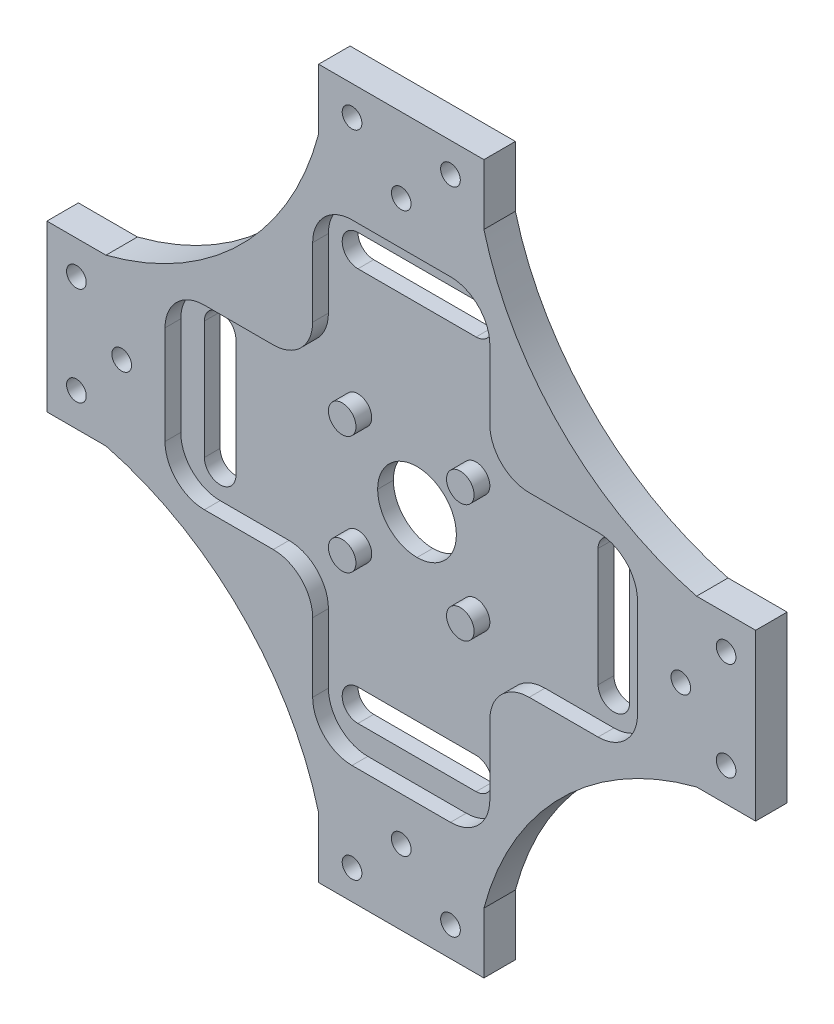
SolidWorks part; units mm, degrees
ref_plane "Front Plane" through (0, 0, 0) normal (0, 0, 1) x (1, 0, 0)
ref_plane "Top Plane" through (0, 0, 0) normal (0, 1, 0) x (1, 0, 0)
ref_plane "Right Plane" through (0, 0, 0) normal (1, 0, 0) x (0, 0, -1)
sketch "Sketch1" plane through (0, 0, 0) normal (0, 0, 1) x (1, 0, 0)
  line L13 (-90, -90) -> (90, -90)
  line L14 (-90, -90) -> (-90, 90)
  line L15 (-90, 90) -> (90, 90)
  line L16 (90, -90) -> (90, 90)
  line L17 (-90, -90) -> (90, 90) construction
  line L18 (-90, 90) -> (90, -90) construction
  line L19 (-75, -75) -> (75, -75)
  line L20 (-75, -75) -> (-75, 75)
  line L21 (-75, 75) -> (75, 75)
  line L22 (75, -75) -> (75, 75)
  line L23 (-75, -75) -> (75, 75) construction
  line L24 (-75, 75) -> (75, -75) construction
  line L39 (-75, -24.9122) -> (-75, 26.5574)
  line L40 (75, 22.5) -> (75, -22.5)
  line L41 (75, -22.5) -> (90, -20.9897)
  line L42 (90, -20.9897) -> (90, 20.9897)
  line L43 (90, 20.9897) -> (75, 22.5)
  line L44 (20.9897, -90) -> (22.5, -75)
  line L45 (22.5, -75) -> (-22.5, -75)
  line L46 (-22.5, -75) -> (-20.9897, -90)
  line L47 (-20.9897, -90) -> (20.9897, -90)
  line L48 (-90, -20.9897) -> (-75, -22.5)
  line L49 (-75, -22.5) -> (-75, 22.5)
  line L50 (-75, 22.5) -> (-90, 20.9897)
  line L51 (-90, 20.9897) -> (-90, -20.9897)
  line L52 (-20.9897, 90) -> (-22.5, 75)
  line L53 (-22.5, 75) -> (22.5, 75)
  line L54 (22.5, 75) -> (20.9897, 90)
  line L55 (20.9897, 90) -> (-20.9897, 90)
  line L64 (-72, -72) -> (-72, 72)
  line L65 (-72, 72) -> (72, 72)
  line L70 (72, -72) -> (72, 72)
  line L71 (-72, -72) -> (72, -72)
  line L72 (-10.5, -75) -> (10.5, -75)
  line L77 (75, -10.5) -> (64, -10.5)
  line L78 (75, -10.5) -> (75, 10.5)
  line L79 (75, 10.5) -> (64, 10.5)
  line L80 (64, -10.5) -> (64, 10.5)
  line L81 (-10.5, -75) -> (-10.5, -64)
  line L82 (-10.5, -64) -> (10.5, -64)
  line L83 (10.5, -75) -> (10.5, -64)
  line L84 (-75, 10.5) -> (-75, -10.5)
  line L85 (-75, 10.5) -> (-64, 10.5)
  line L86 (-64, 10.5) -> (-64, -10.5)
  line L87 (-75, -10.5) -> (-64, -10.5)
  line L88 (10.5, 75) -> (-10.5, 75)
  line L89 (10.5, 75) -> (10.5, 64)
  line L90 (10.5, 64) -> (-10.5, 64)
  line L91 (-10.5, 75) -> (-10.5, 64)
  line L92 (-75, 45) -> (-72, 45)
  line L93 (-45, 75) -> (-45, 72)
  circle A0 centre (82.5, 12.5) radius 2.5
  circle A1 centre (71, 0) radius 2.5
  circle A2 centre (82.5, -12.5) radius 2.5
  circle A3 centre (12.5, -82.5) radius 2.5
  circle A4 centre (0, -71) radius 2.5
  circle A5 centre (-12.5, -82.5) radius 2.5
  circle A6 centre (-82.5, -12.5) radius 2.5
  circle A7 centre (-71, 0) radius 2.5
  circle A8 centre (-82.5, 12.5) radius 2.5
  circle A9 centre (-12.5, 82.5) radius 2.5
  circle A10 centre (0, 71) radius 2.5
  circle A11 centre (12.5, 82.5) radius 2.5
  point P0 (0, 0)
  point P11 (0, 0)
  point P74 (64, 0)
  point P85 (0, 0)
  dimension "D3" = 4
  dimension "D1" = 180
  dimension "D2" = 180
  dimension "D4" = 150
  dimension "D5" = 4
  dimension "D6" = 3
  dimension "D8" = 11
  dimension "D7" = 21
  dimension "D10" = 45
  dimension "D11" = 45
  dimension "D9" = 4
extrude "Boss-Extrude1" add sketch "Sketch1" along normal mid plane 8 contours L19 L22 L21 L20 A10 A7 A4 A1 | L42 L15 L40 L21 A11 A9 | L47 L16 L45 L22 A2 A0 | L14 L20 A8 A6 | L51 L13 L49 L19 A5 A3 | A1 L79 L80 L77 | A1 L77 L40 L79 | L91 L21 L20 L39 L85 L64 L65 | A10 L65 L89 L53 L91 | A10 L65 L91 L90 L89 | A4 L71 L83 L82 L81 | A4 L71 L81 L45 L83 | L83 L19 L22 L77 L70 L71 | A7 L64 L87 L86 L85 | A7 L64 L85 L49 L87 | L91 L65 L64 L85 L86 L87 L71 L81 L82 L83 L70 L77 L80 L79 L89 L90 | L21 L93 L65 L91 | L21 L89 L65 L70 L79 L22 | L93 L21 L20 L92 L64 L65 region at (0, -82.4076, 0) region at (-82.4076, 0, 0) region at (-48.75, -74.0878, 0) region at (16.5, -74.0878, 0) region at (0, -73.5752, 0) region at (-73.5, 27.75, 0) region at (-73.5752, 0, 0) region at (82.4076, 0, 0) region at (0, -67.765, 0) region at (0, 0, 0) region at (0, 82.4076, 0) region at (-67.765, 0, 0) region at (-27.75, 73.5, 0) region at (-74.5757, 60, 0) region at (74.0878, 16.5, 0) region at (73.5752, 0, 0) region at (0, 73.5752, 0) region at (67.765, 0, 0) region at (0, 67.765, 0)
sketch "Sketch6" plane through (0, 0, 0) normal (0, 0, 1) x (1, 0, 0)
  line L7 (-15, 50) -> (15, 50) construction
  line L9 (-15, 54) -> (15, 54)
  line L16 (0, -55) -> (0, 55) construction
  line L18 (55, 0) -> (-55, 0) construction
  line L24 (-15, 46) -> (15, 46)
  line L25 (-20.9897, -90) -> (20.9897, -90)
  line L26 (-20.9897, -90) -> (-20.9897, 90)
  line L27 (-20.9897, 90) -> (20.9897, 90)
  line L28 (20.9897, -90) -> (20.9897, 90)
  line L29 (-20.9897, -90) -> (20.9897, 90) construction
  line L30 (-20.9897, 90) -> (20.9897, -90) construction
  line L31 (-90, -20.9897) -> (90, -20.9897)
  line L32 (-90, -20.9897) -> (-90, 20.9897)
  line L33 (-90, 20.9897) -> (90, 20.9897)
  line L34 (90, -20.9897) -> (90, 20.9897)
  line L35 (-90, -20.9897) -> (90, 20.9897) construction
  line L36 (-90, 20.9897) -> (90, -20.9897) construction
  line L37 (50, 15) -> (50, -15) construction
  line L38 (54, 15) -> (54, -15)
  line L39 (46, 15) -> (46, -15)
  line L40 (15, -50) -> (-15, -50) construction
  line L41 (15, -54) -> (-15, -54)
  line L42 (15, -46) -> (-15, -46)
  line L43 (-50, -15) -> (-50, 15) construction
  line L44 (-54, -15) -> (-54, 15)
  line L45 (-46, -15) -> (-46, 15)
  line L47 (-10, -10) -> (10, -10)
  line L48 (-10, -10) -> (-10, 10)
  line L49 (-10, 10) -> (10, 10)
  line L50 (10, -10) -> (10, 10)
  line L51 (-10, -10) -> (10, 10) construction
  line L52 (-10, 10) -> (10, -10) construction
  line L54 (-20, -20) -> (20, -20)
  line L55 (-20, -20) -> (-20, 20)
  line L56 (-20, 20) -> (20, 20)
  line L57 (20, -20) -> (20, 20)
  line L58 (-20, -20) -> (20, 20) construction
  line L59 (-20, 20) -> (20, -20) construction
  arc A3 (-75, 20.9897) -> (-20.9897, 74.6397) centre (-93.7618, 93.889) ccw
  arc A4 (-15, 54) -> (-15, 46) centre (-15, 50) ccw
  arc A5 (15, 46) -> (15, 54) centre (15, 50) ccw
  arc A6 (54, 15) -> (46, 15) centre (50, 15) ccw
  arc A7 (46, -15) -> (54, -15) centre (50, -15) ccw
  arc A8 (15, -54) -> (15, -46) centre (15, -50) ccw
  arc A9 (-15, -46) -> (-15, -54) centre (-15, -50) ccw
  arc A10 (-54, -15) -> (-46, -15) centre (-50, -15) ccw
  arc A11 (-46, 15) -> (-54, 15) centre (-50, 15) ccw
  arc A12 (75, 20.9897) -> (20.9897, 74.6397) centre (93.7618, 93.889) cw
  arc A13 (75, -20.9897) -> (20.9897, -74.6397) centre (93.7618, -93.889) ccw
  arc A14 (-75, -20.9897) -> (-20.9897, -74.6397) centre (-93.7618, -93.889) cw
  point P0 (0, 0)
  point P5 (0, 0)
  point P14 (0, 50)
  point P36 (0, 0)
  point P40 (50, 0)
  point P47 (0, -50)
  point P54 (-50, 0)
  point P62 (0, 0)
  point P70 (0, 0)
  dimension "D1" = 20
  dimension "D7" = 40
  dimension "D2" = 50
  dimension "D3" = 8
  dimension "D4" = 30
  dimension "D6" = 20
  dimension "D8" = 40
  dimension "D5" = 4
extrude "Cut-Extrude15" cut sketch "Sketch6" against normal mid plane 10 flip side to cut contours L33 L26 | L26 L33 L28 L27 A5 L24 A4 L9 | L28 L33 | L33 L26 L31 L28 L50 L47 L48 L49 | L31 L26 L25 L28 A9 L42 A8 L41 | L45 A11 L44 A10 | L39 A7 L38 A6 | L31 L26 | L28 L31 | L33 L34 L31 L32 | L38 A7 L39 A6 | L47 L50 L49 L48 region at (0, -56.1067, 0) region at (-35.4696, -35.3958, 0) region at (35.4696, -35.3958, 0) region at (-20.396, 0, 0) region at (-35.4696, 35.3958, 0) region at (0, 56.1067, 0) region at (35.4696, 35.3958, 0) region at (50, 0, 0) region at (-50, 0, 0) region at (-19.4343, 0, 0)
sketch "Sketch8" plane through (0, 0, 0) normal (0, 0, 1) x (1, 0, 0)
  line L1 (-60, -22.5) -> (60, -22.5)
  line L2 (-60, -22.5) -> (-60, 22.5)
  line L3 (-60, 22.5) -> (60, 22.5)
  line L4 (60, -22.5) -> (60, 22.5)
  line L5 (-60, -22.5) -> (60, 22.5) construction
  line L6 (-60, 22.5) -> (60, -22.5) construction
  line L7 (-22.5, -60) -> (22.5, -60)
  line L8 (-22.5, -60) -> (-22.5, 60)
  line L9 (-22.5, 60) -> (22.5, 60)
  line L10 (22.5, -60) -> (22.5, 60)
  line L11 (-22.5, -60) -> (22.5, 60) construction
  line L12 (-22.5, 60) -> (22.5, -60) construction
  line L13 (-19, -19) -> (19, -19) construction
  line L14 (-19, -19) -> (-19, 19) construction
  line L15 (-19, 19) -> (19, 19) construction
  line L16 (19, -19) -> (19, 19) construction
  line L17 (-19, -19) -> (19, 19) construction
  line L18 (-19, 19) -> (19, -19) construction
  point P0 (0, 0)
  point P6 (0, 0)
  point P11 (0, 0)
  dimension "D1" = 45
  dimension "D2" = 120
  dimension "D3" = 45
  dimension "D4" = 120
  dimension "D9" = 38
  dimension "D10" = 38
extrude "Cut-Extrude16" cut sketch "Sketch8" against normal blind 4 from surface contours L9 L10 L7 L8 | L3 L4 L1 L2 starting at face at (0, -50, 4)
sketch "Sketch10" plane through (0, 0, 0) normal (0, 0, 1) x (1, 0, 0)
  line L1 (-15, -15) -> (15, -15) construction
  line L2 (-15, -15) -> (-15, 15) construction
  line L3 (-15, 15) -> (15, 15) construction
  line L4 (15, -15) -> (15, 15) construction
  line L5 (-15, -15) -> (15, 15) construction
  line L6 (-15, 15) -> (15, -15) construction
  circle A0 centre (-15, 15) radius 2.5
  circle A1 centre (15, 15) radius 2.5
  circle A2 centre (15, -15) radius 3.5
  circle A3 centre (15, 15) radius 3.5
  circle A4 centre (-15, 15) radius 3.5
  circle A5 centre (-15, -15) radius 3.5
  circle A6 centre (-15, -15) radius 2.5
  circle A7 centre (15, -15) radius 2.5
  point P0 (0, 0)
  point P14 (0, 0)
  dimension "D1" = 7
  dimension "D2" = 5
  dimension "D3" = 7
  dimension "D4" = 5
  dimension "D5" = 5
  dimension "D6" = 7
  dimension "D7" = 5
  dimension "D8" = 7
  dimension "D9" = 30
  dimension "D10" = 30
extrude "Boss-Extrude3" add sketch "Sketch10" along normal blind 4 contours A1 | A3 A1 | A4 | A2 | A5 region at (15, 15, 0) region at (11.599, 15, 0)
extrude "Cut-Extrude17" cut sketch "Sketch10<3>" along normal blind 6 from surface contours A1 | A0 | A6 | A7 region at (-15, 15, 0) region at (15, 15, 0) region at (-15, -15, 0) region at (15, -15, 0) starting at face at (0, -50, -4)
sketch "Sketch10<3>" plane through (0, 0, 0) normal (0, 0, 1) x (1, 0, 0) same geometry as "Sketch10"
fillet "Fillet1" radius 10 16 edges at (-22.5, -60, 2) (22.5, -60, 2) (60, -22.5, 2) (60, 22.5, 2) (22.5, 60, 2) (-22.5, 60, 2) (-60, 22.5, 2) (-60, -22.5, 2) (10, -10, -2) (-10, -10, -2) (10, 10, -2) (-10, 10, -2) (22.5, -22.5, 2) (-22.5, -22.5, 2) (22.5, 22.5, 2) (-22.5, 22.5, 2)
